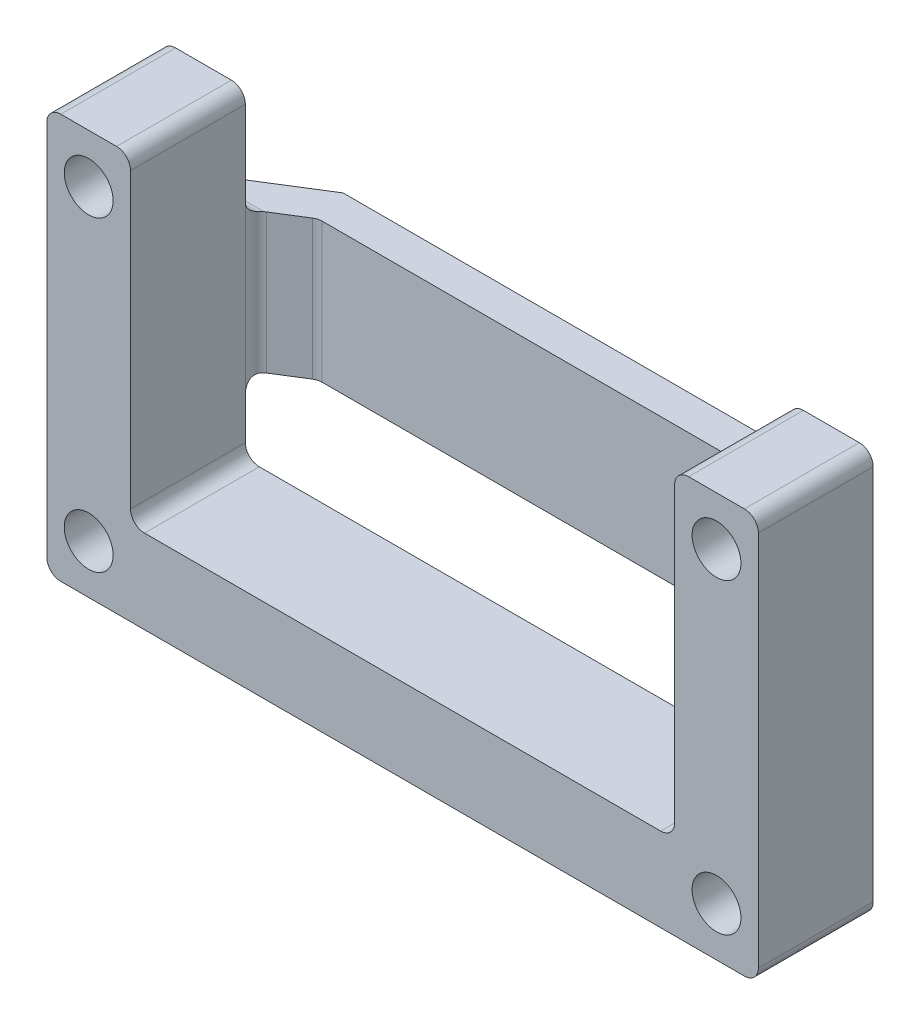
SolidWorks part; units mm, degrees
material "PLA"
ref_plane "前视基准面" through (0, 0, 0) normal (0, 0, 1) x (1, 0, 0)
ref_plane "上视基准面" through (0, 0, 0) normal (0, 1, 0) x (1, 0, 0)
ref_plane "右视基准面" through (0, 0, 0) normal (1, 0, 0) x (0, 0, -1)
sketch "草图1" plane through (0, 0, 0) normal (0, 0, 1) x (1, 0, 0)
  line L0 (-19.5, 14.5) -> (-19.5, -8.5)
  line L1 (-25.5, 14.5) -> (-19.5, 14.5)
  line L2 (-25.5, 14.5) -> (-25.5, -14.5)
  line L3 (-25.5, -14.5) -> (25.5, -14.5)
  line L4 (25.5, 14.5) -> (25.5, -14.5)
  line L5 (-25.5, 14.5) -> (25.5, -14.5) construction
  line L6 (-25.5, -14.5) -> (25.5, 14.5) construction
  line L7 (-19.5, -8.5) -> (19.5, -8.5)
  line L8 (19.5, -8.5) -> (19.5, 14.5)
  line L9 (-19.5, 14.5) -> (19.5, 14.5) construction
  line L10 (19.5, 14.5) -> (25.5, 14.5)
  line L11 (-22.5, 14.5) -> (-22.5, -14.5) construction
  line L12 (22.5, 14.5) -> (22.5, -14.5) construction
  point P0 (0, 0)
  dimension "D1" = 29
  dimension "D2" = 45
  dimension "D3" = 6
  dimension "D4" = 6
extrude "凸台-拉伸1" add sketch "草图1" along normal blind 8.23
sketch "草图3" plane through (0, 0, 8.23) normal (0, 0, 1) x (1, 0, 0)
  line L1 (-22.5, 11) -> (22.5, 11) construction
  line L2 (-22.5, 11) -> (-22.5, -11) construction
  line L3 (-22.5, -11) -> (22.5, -11) construction
  line L4 (22.5, 11) -> (22.5, -11) construction
  line L5 (-22.5, 11) -> (22.5, -11) construction
  line L6 (-22.5, -11) -> (22.5, 11) construction
  circle A4 centre (-22.5, 11) radius 1.75
  circle A5 centre (-22.5, -11) radius 1.75
  circle A6 centre (22.5, -11) radius 1.75
  circle A7 centre (22.5, 11) radius 1.75
  point P0 (0, 0)
  dimension "D3" = 3.5
  dimension "D1" = 22
  dimension "D2" = 45
extrude "切除-拉伸2" cut sketch "草图3" against normal through all
fillet "圆角1" radius 1 8 edges at (25.5, -14.5, 4.115) (-25.5, -14.5, 4.115) (-25.5, 14.5, 4.115) (-19.5, 14.5, 4.115) (-19.5, -8.5, 4.115) (19.5, -8.5, 4.115) (19.5, 14.5, 4.115) (25.5, 14.5, 4.115)
sketch "草图4" plane through (0, 14.5, 0) normal (0, 1, 0) x (1, 0, 0)
  line L0 (25.5, 0) -> (17.5, 5)
  line L1 (17.5, 5) -> (-17.5, 5)
  line L2 (-17.5, 5) -> (-25.5, 0)
  line L3 (18.5, 0) -> (-18.5, 0) construction
  line L4 (0, 0) -> (0, 5) construction
  dimension "D1" = 5
  dimension "D2" = 35
extrude "拉伸-薄壁1" add sketch "草图4" against normal blind 10 from offset 8 thin thin type one direction reverse wall 2.5 offset against normal yes
fillet "圆角2" radius 1 8 edges at (-23.1415, 6.5, 0) (-23.1415, -3.5, 0) (23.1415, -3.5, 0) (23.1415, 6.5, 0) (16.783, 1.5, -2.5) (20.783, 1.5, 0) (-20.783, 1.5, 0) (-16.783, 1.5, -2.5)
